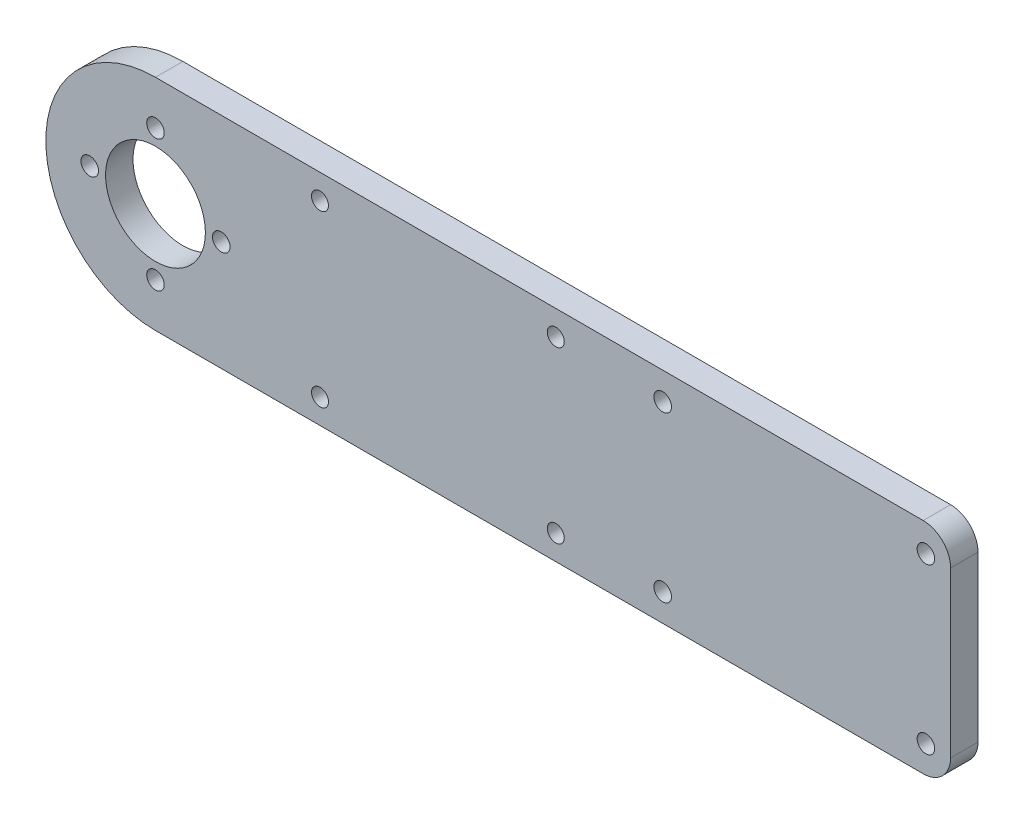
SolidWorks part; units mm, degrees
material "Acrylic (Medium-high impact)"
ref_plane "Front Plane" through (0, 0, 0) normal (0, 0, 1) x (1, 0, 0)
ref_plane "Top Plane" through (0, 0, 0) normal (0, 1, 0) x (1, 0, 0)
ref_plane "Right Plane" through (0, 0, 0) normal (1, 0, 0) x (0, 0, -1)
sketch "Sketch2" plane through (0, 0, 0) normal (0, 0, 1) x (1, 0, 0)
  line L0 (0, 20) -> (0, -20)
  line L1 (0, 20) -> (145, 20)
  line L2 (0, -20) -> (145, -20)
  line L3 (145, 20) -> (145, -20)
  line L4 (0, 0) -> (-20, 0)
  circle A0 centre (0, 0) radius 20
  circle A1 centre (0, 0) radius 9.1
  dimension "D1" = 40
  dimension "D3" = 18.2
  dimension "D2" = 165
extrude "Boss-Extrude1" add sketch "Sketch2" along normal mid plane 5 contours A1 L0 A0 | A0 L2 L3 L1 | A1 L4 A0 L0 | A1 L0 A0 L4 region at (9.696, 0, 0) region at (80.2769, 0, 0) region at (-9.696, 9.696, 0) region at (-9.696, -9.696, 0)
fillet "Fillet1" radius 5 2 edges at (145, -20, 0) (145, 20, 0)
sketch "Sketch3" plane through (0, 0, -2.5) normal (0, 0, -1) x (-1, 0, 0)
  line L0 (-51.5, 20) -> (-51.5, -20)
  line L1 (-51.5, 0) -> (-30, 0)
  line L2 (-30, 0) -> (-30, 15.5)
  line L3 (-145, 15) -> (-145, -15)
  line L4 (-140, -20) -> (0, -20)
  line L5 (0, 20) -> (-140, 20)
  line L6 (-145, 15) -> (-145, -15)
  line L7 (-140, -20) -> (0, -20)
  line L8 (0, 20) -> (-140, 20)
  line L9 (-51.5, 0) -> (-116.5, 0)
  line L10 (-116.5, 0) -> (-116.5, 15)
  line L11 (-116.5, 15) -> (-140.5, 15)
  line L12 (0, 0) -> (0, 12)
  circle A0 centre (0, 0) radius 12
  circle A1 centre (-30, 15.5) radius 1.55
  circle A2 centre (-30, -15.5) radius 1.55
  arc A3 (-145, -15) -> (-140, -20) centre (-140, -15) ccw
  arc A4 (0, -20) -> (0, 20) centre (0, 0) ccw
  arc A5 (-140, 20) -> (-145, 15) centre (-140, 15) ccw
  arc A6 (-145, -15) -> (-140, -20) centre (-140, -15) ccw
  arc A7 (0, -20) -> (0, 20) centre (0, 0) ccw
  arc A8 (-140, 20) -> (-145, 15) centre (-140, 15) ccw
  circle A9 centre (-73, -15.5) radius 1.55
  circle A10 centre (-73, 15.5) radius 1.55
  circle A11 centre (-140.5, 15) radius 1.6
  circle A12 centre (-140.5, -15) radius 1.6
  circle A13 centre (-92.5, -15) radius 1.6
  circle A14 centre (-92.5, 15) radius 1.6
  circle A15 centre (0, 12) radius 1.6
  circle A16 centre (12, 0) radius 1.6
  circle A17 centre (0, -12) radius 1.6
  circle A18 centre (-12, 0) radius 1.6
  dimension "D2" = 24
  dimension "D6" = 3.1
  dimension "D10" = 3.2
  dimension "D11" = 3.2
  dimension "D3" = 21.5
  dimension "D4" = 15.5
  dimension "D5" = 30
  dimension "D7" = 65
  dimension "D8" = 15
  dimension "D9" = 24
  dimension "D1" = 0
  dimension "D12" = 4
extrude "Cut-Extrude1" cut sketch "Sketch3" against normal through all contours A14 | A13 | A11 | A12 | A0 A16 | A0 A16 | A0 A17 | A2 | A9 | A10 | A1 | A18 | A15 | A17 region at (142.0547, 15, -2.5) region at (-12.6595, 0, -2.5) region at (-11.3021, 0, -2.5) region at (0, -12.6595, -2.5) region at (140.5, -15, -2.5) region at (92.5, -15, -2.5) region at (92.5, 15, -2.5)
